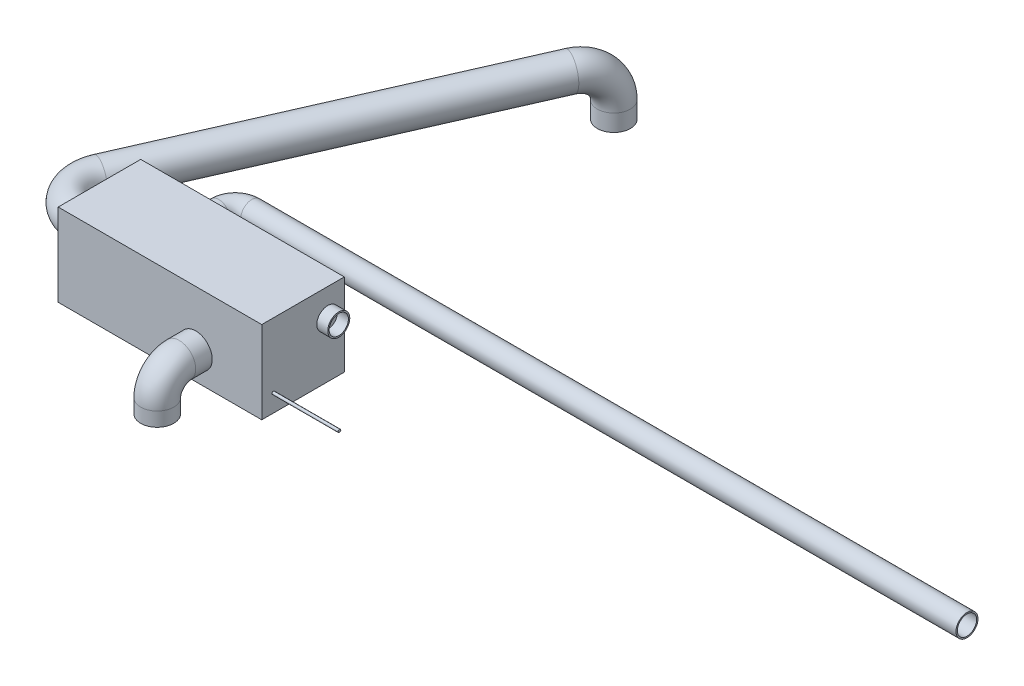
SolidWorks part; units mm, degrees
ref_plane "Front" through (0, 0, 0) normal (0, 0, 1) x (1, 0, 0)
ref_plane "Top" through (0, 0, 0) normal (0, 1, 0) x (1, 0, 0)
ref_plane "Right" through (0, 0, 0) normal (1, 0, 0) x (0, 0, -1)
sketch "Sketch1" plane through (0, 0, 0) normal (0, 1, 0) x (1, 0, 0)
  line L1 (-469.9, 190.5) -> (469.9, 190.5)
  line L2 (-469.9, 190.5) -> (-469.9, -190.5)
  line L3 (-469.9, -190.5) -> (469.9, -190.5)
  line L4 (469.9, 190.5) -> (469.9, -190.5)
  line L5 (-469.9, 190.5) -> (469.9, -190.5) construction
  line L6 (-469.9, -190.5) -> (469.9, 190.5) construction
  point P0 (0, 0)
  dimension "D1" = 381
  dimension "D2" = 939.8
extrude "Boss-Extrude1" add sketch "Sketch1" along normal blind 381
sketch "Sketch2" plane through (0, 0, 190.5) normal (0, 0, 1) x (1, 0, 0)
  line L0 (469.9, 381) -> (469.9, 0) construction
  line L1 (-469.9, 381) -> (469.9, 381) construction
  circle A0 centre (165.1, 127) radius 76.2
  circle A1 centre (165.1, 127) radius 69.85
  dimension "D1" = 152.4
  dimension "D3" = 254
  dimension "D4" = 139.7
  dimension "D2" = 304.8
extrude "Boss-Extrude2" add sketch "Sketch2" along normal blind 50.8
sketch "Sketch3" plane through (469.9, 0, 0) normal (1, 0, 0) x (0, 0, -1)
  line L0 (-190.5, 381) -> (190.5, 381) construction
  line L1 (190.5, 381) -> (190.5, 0) construction
  circle A0 centre (114.3, 254) radius 50.8
  circle A1 centre (114.3, 254) radius 44.45
  dimension "D1" = 101.6
  dimension "D2" = 88.9
  dimension "D3" = 127
  dimension "D4" = 76.2
extrude "Boss-Extrude3" add sketch "Sketch3" along normal blind 50.8
sketch "Sketch4" plane through (469.9, 0, 0) normal (1, 0, 0) x (0, 0, -1)
  circle A0 centre (-136.8501, 81.3511) radius 6.35
  dimension "D1" = 12.7
extrude "Boss-Extrude4" add sketch "Sketch4" along normal blind 304.8
sketch "Sketch5" plane through (0, 0, -190.5) normal (0, 0, -1) x (-1, 0, 0)
  line L0 (-469.9, 381) -> (469.9, 381) construction
  line L1 (469.9, 381) -> (469.9, 0) construction
  circle A0 centre (185.6926, 273.8882) radius 50.8
  circle A1 centre (185.6926, 273.8882) radius 44.45
  dimension "D1" = 101.6
  dimension "D2" = 88.9
  dimension "D4" = 284.2074
  dimension "D3" = 107.1118
extrude "Boss-Extrude5" add sketch "Sketch5" along normal blind 50.8
sketch "Sketch6" plane through (-469.9, 0, 0) normal (-1, 0, 0) x (0, 0, 1)
  line L0 (-190.5, 381) -> (190.5, 0) construction
  circle A0 centre (0, 190.5) radius 76.2
  circle A1 centre (0, 190.5) radius 69.85
  dimension "D1" = 152.4
  dimension "D2" = 139.7
extrude "Boss-Extrude6" add sketch "Sketch6" along normal blind 50.8
sketch "Sketch7" plane through (0, 0, 241.3) normal (0, 0, 1) x (1, 0, 0)
  circle A0 centre (165.1, 127) radius 76.2 construction
  circle A1 centre (165.1, 127) radius 76.2
  circle A2 centre (165.1, 127) radius 69.85 construction
  circle A3 centre (165.1, 127) radius 69.85
ref_point "Point1"
ref_plane "Plane1" through (165.1, 0, 0) normal (1, 0, 0) x (0, 0, -1)
sketch "Sketch8" plane through (165.1, 0, 0) normal (1, 0, 0) x (0, 0, -1)
  line L0 (-241.3, 127) -> (-266.7, 127)
  line L1 (-241.3, 203.2) -> (-241.3, 50.8) construction
  line L2 (-368.3, 25.4) -> (-368.3, -39.6174)
  arc A0 (-266.7, 127) -> (-368.3, 25.4) centre (-266.7, 25.4) ccw
  dimension "D3" = 101.6
  dimension "D1" = 65.0174
  dimension "D2" = 25.4
sweep "Sweep1" add profiles "Sketch7" path "Sketch8"
ref_point "Point2"
ref_plane "Plane2" through (0, 190.5, 0) normal (0, 1, 0) x (1, 0, 0)
sketch "Sketch9" plane through (0, 190.5, 0) normal (0, 1, 0) x (1, 0, 0)
  line L0 (-520.7, 0) -> (-546.1, 0)
  line L1 (-520.7, 76.2) -> (-520.7, -76.2) construction
  line L2 (-685.6043, 213.7539) -> (-31.1624, 1701.8)
  line L3 (0, 0) -> (0, 1701.8) construction
  line L4 (0, 1701.8) -> (-31.1624, 1701.8) construction
  arc A0 (-546.1, 0) -> (-685.6043, 213.7539) centre (-546.1, 152.4) cw
  dimension "D2" = 152.4
  dimension "D1" = 25.4
  dimension "D3" = 1625.6
  dimension "D4" = 1701.8
sketch "Sketch10" plane through (-520.7, 0, 0) normal (-1, 0, 0) x (0, 0, 1)
  circle A0 centre (0, 190.5) radius 76.2 construction
  circle A1 centre (0, 190.5) radius 76.2
  circle A2 centre (0, 190.5) radius 69.85 construction
  circle A3 centre (0, 190.5) radius 69.85
sweep "Sweep2" add profiles "Sketch10" path "Sketch9"
ref_point "Point3"
ref_point "Point4"
ref_plane "Plane3" through (622.0954, 0, -1414.4976) normal (0.4026, 0, -0.9154) x (-0.9154, 0, -0.4026)
ref_plane "Plane4" through (-653.2577, 0, -287.3024) normal (0.9154, 0, 0.4026) x (0.4026, 0, -0.9154)
sketch "Sketch12" plane through (-318.4648, 0, -1048.5423) normal (0.9154, 0, 0.4026) x (0.4026, 0, -0.9154)
  line L0 (739.0444, 190.5) -> (688.2444, 190.5) construction
  line L1 (535.8444, 38.1) -> (535.8444, -39.6174) construction
  line L2 (-1178.477, -39.6174) -> (-1026.077, -39.6174) construction
  line L3 (713.6444, 190.5) -> (713.6444, 114.3) construction
  line L4 (891.4444, 38.1) -> (891.4444, -39.6174)
  line L5 (739.0444, 190.5) -> (713.6444, 190.5)
  arc A0 (688.2444, 190.5) -> (535.8444, 38.1) centre (688.2444, 38.1) ccw construction
  arc A1 (739.0444, 190.5) -> (891.4444, 38.1) centre (739.0444, 38.1) cw
  dimension "D2" = 152.4
  dimension "D1" = 25.4
sketch "Sketch11" plane through (622.0954, 0, -1414.4976) normal (0.4026, 0, -0.9154) x (-0.9154, 0, -0.4026)
  circle A0 centre (713.6444, 190.5) radius 69.85 construction
  circle A1 centre (713.6444, 190.5) radius 76.2
  circle A2 centre (713.6444, 190.5) radius 76.2
  circle A3 centre (713.6444, 190.5) radius 69.85
  dimension "D1" = 0
sweep "Sweep4" add profiles "Sketch11" path "Sketch12"
ref_point "Point5"
ref_plane "Plane5" through (0, 273.8882, 0) normal (0, 1, 0) x (1, 0, 0)
sketch "Sketch13" plane through (0, 273.8882, 0) normal (0, 1, 0) x (1, 0, 0)
  line L0 (-185.6926, 241.3) -> (-185.6926, 266.7)
  line L1 (-134.8926, 241.3) -> (-236.4926, 241.3) construction
  line L2 (-109.4926, 342.9) -> (3192.5074, 342.9)
  arc A0 (-185.6926, 266.7) -> (-109.4926, 342.9) centre (-109.4926, 266.7) cw
  dimension "D1" = 76.2
  dimension "D2" = 25.4
  dimension "D3" = 3302
sketch "Sketch14" plane through (0, 0, -241.3) normal (0, 0, -1) x (-1, 0, 0)
  circle A0 centre (185.6926, 273.8882) radius 44.45 construction
  circle A1 centre (185.6926, 273.8882) radius 50.8
  circle A2 centre (185.6926, 273.8882) radius 50.8
  circle A3 centre (185.6926, 273.8882) radius 44.45
  dimension "D1" = 0
sweep "Sweep5" add profiles "Sketch14" path "Sketch13"
sketch "Sketch15" [suppressed] plane through (0, 273.8882, 0) normal (0, 1, 0) x (1, 0, 0)
  line L0 (-185.6926, 241.3) -> (-185.6926, 317.5)
  line L1 (-134.8926, 241.3) -> (-236.4926, 241.3) construction
  line L2 (-177.0378, 383.24) -> (204.2544, 1806.242)
  line L3 (469.9, 190.5) -> (-469.9, 190.5) construction
  line L4 (221.5641, 1937.722) -> (221.5641, 2852.122)
  arc A0 (-185.6926, 317.5) -> (-177.0378, 383.24) centre (68.3074, 317.5) cw
  arc A1 (204.2544, 1806.242) -> (221.5641, 1937.722) centre (-286.4359, 1937.722) ccw
  dimension "D2" = 254
  dimension "D4" = 508
  dimension "D1" = 76.2
  dimension "D3" = 75
  dimension "D5" = 914.4
  dimension "D6" = 1473.2
sketch "Sketch16" [suppressed] plane through (0, 0, -241.3) normal (0, 0, -1) x (-1, 0, 0)
  circle A0 centre (185.6926, 273.8882) radius 44.45 construction
  circle A1 centre (185.6926, 273.8882) radius 50.8
  circle A2 centre (185.6926, 273.8882) radius 50.8
  circle A3 centre (185.6926, 273.8882) radius 44.45
  dimension "D1" = 0
sweep "Sweep6" [suppressed] add profiles "Sketch16" path "Sketch15"
